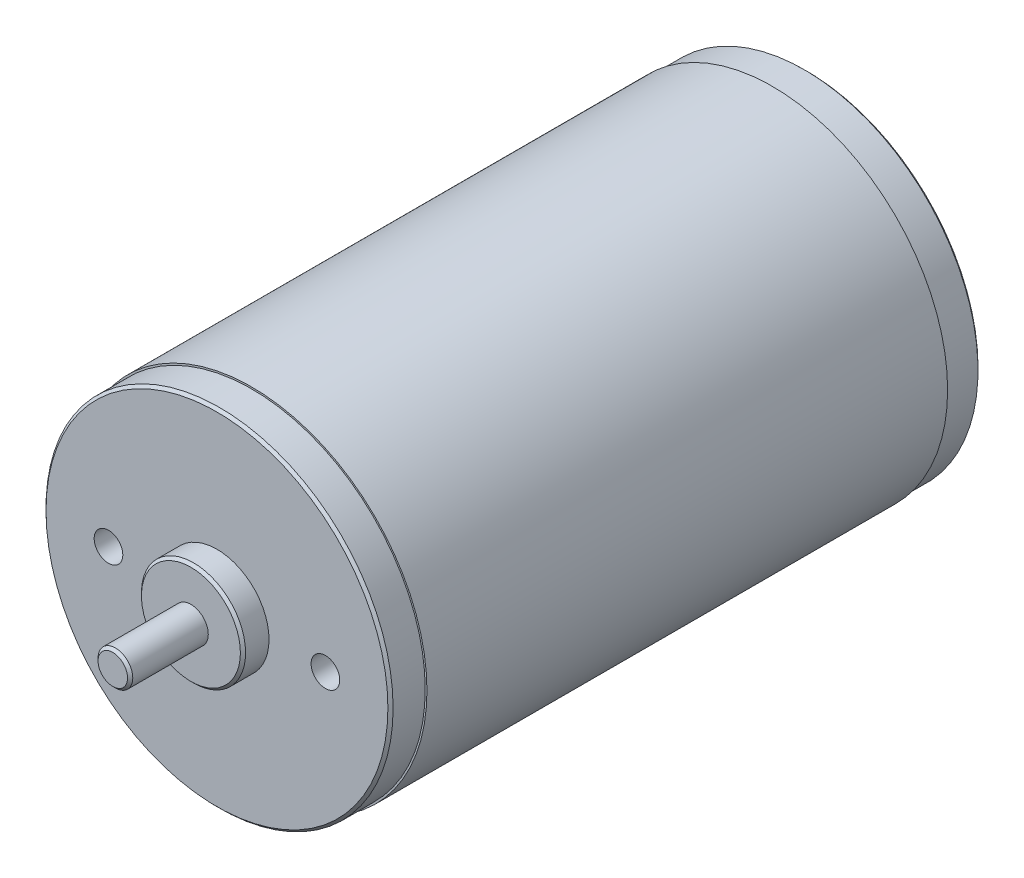
SolidWorks part; units mm, degrees
ref_plane "Front Plane" through (0, 0, 0) normal (0, 0, 1) x (1, 0, 0)
ref_plane "Top Plane" through (0, 0, 0) normal (0, 1, 0) x (1, 0, 0)
ref_plane "Right Plane" through (0, 0, 0) normal (1, 0, 0) x (0, 0, -1)
sketch "Sketch1" plane through (0, 0, 0) normal (0, 1, 0) x (1, 0, 0)
  line L0 (20.2, 64) -> (0, 64)
  line L1 (0, 64) -> (0, 4)
  line L2 (0, 4) -> (20.2, 4)
  line L3 (20.2, 4) -> (20.2, 64)
  line L4 (0, 64) -> (0, 4) construction
revolve "Revolve1" add sketch "Sketch1" angle 360 about L4 reverse direction yes
sketch "Sketch2" plane through (0, 0, -4) normal (0, 0, 1) x (1, 0, 0)
  circle A0 centre (0, 0) radius 20
extrude "Boss-Extrude1" add sketch "Sketch2" along normal blind 4
sketch "Sketch3" plane through (0, 0, 0) normal (0, 0, 1) x (1, 0, 0)
  circle A0 centre (0, 0) radius 6
extrude "Boss-Extrude2" add sketch "Sketch3" along normal blind 3
sketch "Sketch4" plane through (0, 0, 3) normal (0, 0, 1) x (1, 0, 0)
  circle A0 centre (0, 0) radius 2
extrude "Boss-Extrude3" add sketch "Sketch4" along normal blind 9
sketch "Sketch5" plane through (0, 0, -64) normal (0, 0, -1) x (-1, 0, 0)
  circle A0 centre (0, 0) radius 20
extrude "Boss-Extrude4" add sketch "Sketch5" along normal blind 4
sketch "Sketch6" plane through (0, 0, -68) normal (0, 0, -1) x (-1, 0, 0)
  circle A0 centre (0, 0) radius 6.325
extrude "Boss-Extrude5" add sketch "Sketch6" along normal blind 1.5
hole_wizard "Ø3.3 (3.3) Diameter Hole1" positions "Sketch8" profile "Sketch7" hole size "Ø3.3" standard "ANSI Metric"
sketch "Sketch8" plane through (0, 0, 0) normal (0, 0, 1) x (1, 0, 0)
  point P0 (-12.5, 0)
  point P1 (12.5, 0)
sketch "Sketch7" plane through (-12.5, 0, 0) normal (1, 0, 0) x (0, -1, 0)
  line L0 (0, 0) -> (0, 9.0914)
  line L1 (0, 9.0914) -> (1.65, 8.1)
  line L2 (1.65, 8.1) -> (1.65, 0)
  line L5 (1.65, 0) -> (0, 0)
  line L10 (0, 9.0914) -> (-1.65, 8.1) construction
  line L11 (0, -6.35) -> (0, 107.95) construction
  dimension "Hole Dia." = 3.3
  dimension "Hole Depth" = 8.1
  dimension "Drill Angle" = 118
chamfer "Chamfer1" distance 0.3 angle 45 5 edges at (-20, 0, -68) (2, 0, 12) (20, 0, 0) (-6.325, 0, -69.5) (6, 0, 3)
ref_plane "Plane1" through (20.2, 0, 0) normal (1, 0, 0) x (0, 0, -1)
sketch "Sketch12" plane through (20.2, 0, 0) normal (1, 0, 0) x (0, 0, -1)
  point P0 (56.4869, 0)
  point P1 (48.9953, 0)
  point P2 (18.2379, -29.7505)
sketch "0_0_Point" plane through (20.2, 0, 0) normal (1, 0, 0) x (0, 0, -1)
  point P0 (48.9953, 0)
other "0_0" parameters "Diameter"=2, "StubLength"=2
ref_axis "Axis3" through (30.2, 0, -48.9953) along (-1, 0, 0)
sketch "0_1_Point" plane through (20.2, 0, 0) normal (1, 0, 0) x (0, 0, -1)
  point P0 (56.4869, 0)
other "0_1" parameters "Diameter"=2, "StubLength"=2
ref_axis "Axis4" through (30.2, 0, -56.4869) along (-1, 0, 0)
